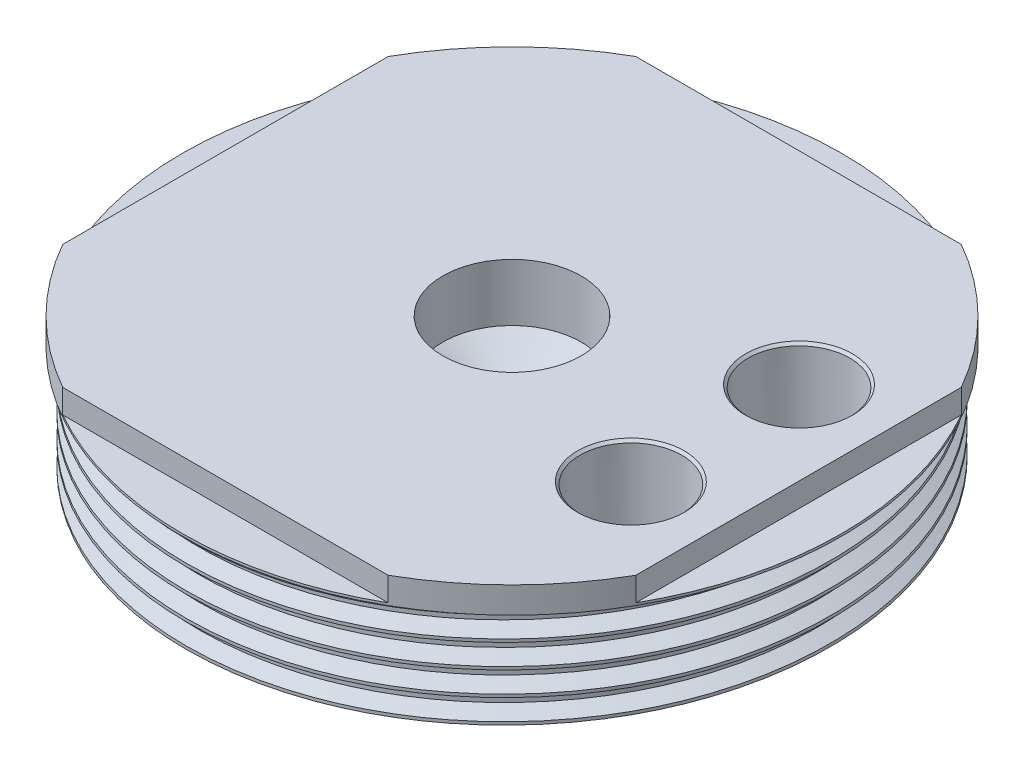
SolidWorks part; units mm, degrees
material "1.0401 (C15)"
ref_plane "Plano frontal" through (0, 0, 0) normal (0, 0, 1) x (1, 0, 0)
ref_plane "Plano superior" through (0, 0, 0) normal (0, 1, 0) x (1, 0, 0)
ref_plane "Plano direito" through (0, 0, 0) normal (1, 0, 0) x (0, 0, -1)
sketch "Esboço1" plane through (0, 0, 0) normal (0, 1, 0) x (1, 0, 0)
  circle A0 centre (0, 0) radius 34.5
  dimension "D1" = 69
extrude "Ressalto-extrusão1" add sketch "Esboço1" against normal blind 13.75
sketch "posição-sensores" plane through (0, 0, 0) normal (0, 1, 0) x (1, 0, 0)
  line L0 (0, 0) -> (21.2492, 8.8017)
  line L1 (0, 0) -> (21.2492, -8.8017)
  line L2 (0, 0) -> (21.2492, 8.8017)
  circle A0 centre (0, 0) radius 34.5
  circle A1 centre (0, 0) radius 23
  dimension "D1" = 69
  dimension "D2" = 46
  dimension "D3" = 23
  dimension "D4" = 45
sketch "Esboço24" plane through (0, 0, 0) normal (0, 1, 0) x (1, 0, 0)
  line L5 (-30, -30) -> (30, -30)
  line L6 (-30, -30) -> (-30, 30)
  line L7 (-30, 30) -> (30, 30)
  line L8 (30, -30) -> (30, 30)
  line L9 (-30, -30) -> (30, 30) construction
  line L10 (-30, 30) -> (30, -30) construction
  circle A0 centre (0, 0) radius 34.5
  circle A1 centre (0, 0) radius 34.5
  circle M13 centre (0, 0) radius 34.5
  dimension "D2" = 69
  dimension "D3" = 60
  dimension "D1" = 90
extrude "chanfro" cut sketch "Esboço24" against normal blind 2.5 contours L8 M13 | L7 M13 | L6 M13 | L5 M13 region at (0, 0, 31.8105) region at (-31.8105, 0, 0) region at (31.8105, 0, 0) region at (0, 0, -31.8105)
hole_wizard "Furo roscado NPT 1/83" positions "3DSketch3" profile "Esboço7" size "1/8" standard "Ansi Inch" end condition through all
sketch3d "3DSketch3"
  point P0 (21.2492, 0, 8.8017)
  point P3 (21.2492, 0, -8.8017)
sketch "Esboço7" plane through (21.2492, 0, 8.8017) normal (1, 0, 0) x (0, 0, 1)
  line L0 (0, 0) -> (0, 13.75)
  line L1 (0, 13.75) -> (4.2164, 13.75)
  line L3 (4.2164, 13.75) -> (4.2164, 13)
  line L4 (4.2164, 13) -> (4.9441, 13)
  line L5 (4.9441, 13) -> (5.3254, 0.2626)
  line L6 (5.3254, 0.2626) -> (5.588, 0)
  line L7 (5.588, 0) -> (0, 0)
  line L8 (0, -6.35) -> (0, 107.95) construction
  line L9 (-5.3254, 0.2626) -> (-5.588, 0) construction
  line L11 (-4.2164, 13) -> (-4.9441, 13) construction
  line L12 (-4.9441, 13) -> (-5.3254, 0.2626) construction
  dimension "Thru Tap Drill Dia." = 8.4328
  dimension "Thru Tap Drill Depth" = 13.75
  dimension "Thread Dia." = 10.6509
  dimension "Thread Angle" = 3.43
  dimension "Thread Depth" = 13
  dimension "Near C'Sink Dia." = 11.176
  dimension "Near C'Sink Angle" = 90
hole_wizard "parafuso-célula" positions "Esboço10" profile "Esboço9" hole size "M16x1.5" standard "Ansi Metric"
sketch "Esboço10" plane through (0, 0, 0) normal (0, 1, 0) x (1, 0, 0)
  point P0 (0, 0)
sketch "Esboço9" plane through (0, 0, 0) normal (1, 0, 0) x (0, 0, 1)
  line L0 (0, 0) -> (0, 10.3562)
  line L1 (0, 10.3562) -> (7.25, 6)
  line L2 (7.25, 6) -> (7.25, 0)
  line L5 (7.25, 0) -> (0, 0)
  line L10 (0, 10.3562) -> (-7.25, 6) construction
  line L11 (0, -6.35) -> (0, 107.95) construction
  dimension "Hole Dia." = 14.5
  dimension "Hole Depth" = 6
  dimension "Drill Angle" = 118
sketch "Esboço29" plane through (0, -13.75, 0) normal (0, -1, 0) x (1, 0, 0)
  circle A0 centre (0, 0) radius 32.35
  circle A1 centre (0, 0) radius 34.5
  dimension "D1" = 64.7
  dimension "D2" = 69
extrude "corte-rosca" cut sketch "Esboço29" against normal blind 11
thread "rosca" pitch 2.5 method extrude trim with start face yes trim with end face yes profile "Perfil da rosca3" start angle 0, offset 2.5, length 0, pitch 2.5, diameter 64.7
ref_plane "Plano3" through (32.35, -16.25, 0) normal (0, 0, 1) x (1, 0, 0)
sketch "Perfil da rosca3" plane through (32.35, -16.25, 0) normal (0, 0, 1) x (1, 0, 0)
  line L0 (0, 0) -> (0, 2.5) construction
  line L1 (0, 0) -> (1.3532, 0.7812)
  line L2 (1.3532, 0.7812) -> (1.3532, 1.0937)
  line L3 (1.3532, 1.0937) -> (0, 1.875)
  line L4 (1.3532, 0.9375) -> (0, 0.9375) construction
  line L11 (0, 0) -> (0, 1.875)
  point P2 (0, 0)
  dimension "Pitch" = 2.5
  dimension "Profile_Angle" = 60
  dimension "Profile_Land" = 0.3125
  dimension "Profile_Height" = 1.3532
